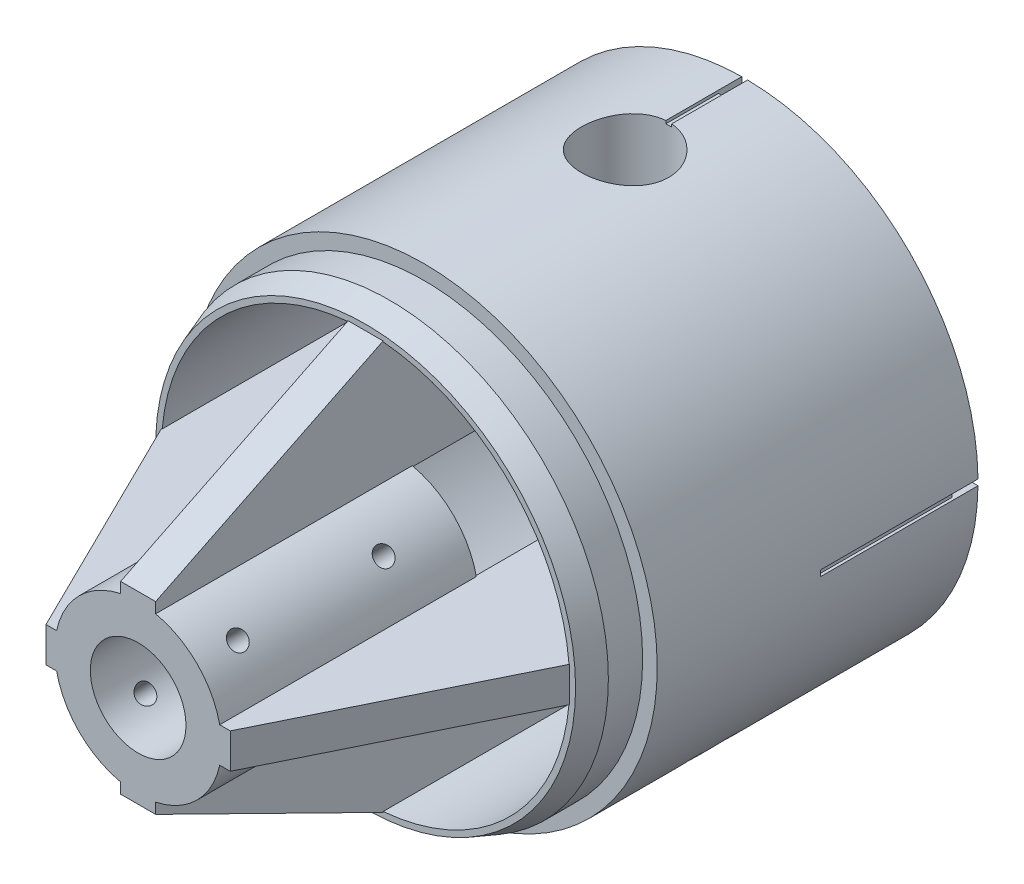
SolidWorks part; units mm, degrees
ref_plane "Piano frontale" through (0, 0, 0) normal (0, 0, 1) x (1, 0, 0)
ref_plane "Piano superiore" through (0, 0, 0) normal (0, 1, 0) x (1, 0, 0)
ref_plane "Piano destro" through (0, 0, 0) normal (1, 0, 0) x (0, 0, -1)
sketch "Schizzo1" plane through (0, 0, 0) normal (0, 0, 1) x (1, 0, 0)
  circle A0 centre (0, 0) radius 40
  circle A1 centre (0, 0) radius 30
  dimension "D1" = 80
  dimension "D2" = 60
extrude "Estrusione-Estrusione1" add sketch "Schizzo1" along normal blind 12.3
sketch "Schizzo2" plane through (0, 0, 12.3) normal (0, 0, 1) x (1, 0, 0)
  circle A0 centre (0, 0) radius 40
  circle A1 centre (0, 0) radius 35
  circle A3 centre (0, 0) radius 40 construction
  dimension "D1" = 5
extrude "Estrusione-Estrusione2" add sketch "Schizzo2" along normal blind 42.7
sketch "Schizzo3" plane through (0, 0, 55) normal (0, 0, 1) x (1, 0, 0)
  circle A0 centre (0, 0) radius 35
  circle A1 centre (0, 0) radius 37.5
  circle A2 centre (0, 0) radius 35 construction
  dimension "D1" = 2.5
extrude "Estrusione-Estrusione3" add sketch "Schizzo3" along normal blind 10
ref_plane "Piano1" through (0, 0, 104) normal (0, 0, 1) x (1, 0, 0)
sketch "Schizzo5" plane through (0, 0, 104) normal (0, 0, 1) x (1, 0, 0)
  circle A0 centre (0, 0) radius 14.3
  circle A1 centre (0, 0) radius 8.2
  dimension "D1" = 28.6
  dimension "D2" = 16.4
extrude "Estrusione-Estrusione4" add sketch "Schizzo5" against normal blind 44 separate body
sketch "Schizzo6" plane through (0, 0, 0) normal (0, 1, 0) x (1, 0, 0)
  line L0 (-35, -26) -> (-35, -65)
  line L1 (-37.5, -65) -> (37.5, -65) construction
  line L2 (-35, -65) -> (-15.8, -104)
  line L3 (-44, -104) -> (44, -104) construction
  line L4 (-15.8, -104) -> (-13.8, -104)
  line L5 (-13.8, -104) -> (-13.8, -26)
  line L6 (-13.8, -26) -> (-35, -26)
  line L7 (-14.3, -60) -> (-14.3, -104) construction
  line L8 (-40, 0) -> (-40, -55) construction
  dimension "D1" = 78
  dimension "D2" = 2
  dimension "D3" = 0.5
  dimension "D4" = 5
extrude "Estrusione-Estrusione5" add sketch "Schizzo6" along normal blind 3 and the other way blind 3
ref_axis "Assi1" through (0, 0, -5.2) along (0, 0, 1)
pattern_circular "RipetizioneCircolare1" count 4 over 360 about axis through (0, 0, -5.2) along (0, 0, 1) of "Estrusione-Estrusione5"
ref_plane "Piano2" through (0, 21.8, 0) normal (0, -1, 0) x (-1, 0, 0)
sketch "Schizzo9" plane through (0, 21.8, 0) normal (0, -1, 0) x (-1, 0, 0)
  line L0 (30, 0) -> (-30, 0) construction
  line L1 (-10, -31) -> (10, -31)
  line L2 (-10, -31) -> (-10, -11)
  line L3 (-10, -11) -> (10, -11)
  line L4 (10, -31) -> (10, -11)
  dimension "D1" = 10
  dimension "D2" = 20
  dimension "D3" = 20
  dimension "D4" = 11
extrude "Estrusione-Estrusione6" add sketch "Schizzo9" against normal blind 15
sketch "Schizzo7" plane through (0, 13.8, 0) normal (0, -1, 0) x (1, 0, 0)
  line L0 (-40, 0) -> (40, 0) construction
  circle A0 centre (0, 20.5) radius 7.5
  dimension "D1" = 15
  dimension "D2" = 20.5
extrude "Taglio-Estrusione1" cut sketch "Schizzo7" against normal through all
ref_plane "Piano3" through (0, 0, 0) normal (0.7071, -0.7071, 0) x (0, 0, 1)
ref_plane "Piano4" through (21.2132, -21.2132, 0) normal (0.7071, -0.7071, 0) x (0, 0, 1)
sketch "Schizzo11" plane through (21.2132, -21.2132, 0) normal (0.7071, -0.7071, 0) x (0, 0, 1)
  circle A0 centre (32, 0) radius 2
  circle A1 centre (38, 0) radius 2
  dimension "D1" = 4
  dimension "D2" = 4
  dimension "D4" = 32
  dimension "D3" = 6
extrude "Taglio-Estrusione2" cut sketch "Schizzo11" along normal through all
sketch "Schizzo12" plane through (0, 0, 60) normal (0, 0, -1) x (-1, 0, 0)
  circle A0 centre (0, 0) radius 8.2
  circle A1 centre (0, 0) radius 4.5
  circle A2 centre (0, 0) radius 8.2 construction
  dimension "D1" = 9
extrude "Estrusione-Estrusione7" add sketch "Schizzo12" against normal blind 4
sketch "Schizzo13" plane through (0, 0, 0) normal (0, 1, 0) x (1, 0, 0)
  line L0 (-2.6, -5.1) -> (-2.6, 0)
  line L1 (-2.6, 0) -> (2.6, 0)
  line L2 (2.6, 0) -> (2.6, -5.1)
  line L3 (40, 0) -> (-40, 0) construction
  circle A0 centre (0, -5.1) radius 2.6
  dimension "D1" = 5.2
  dimension "D2" = 5.1
extrude "Taglio-Estrusione3" cut sketch "Schizzo13" against normal blind 38 contours A0 L2 L1 L0 | A0 region at (0, 0, 1.584) region at (0, 0, 5.1)
sketch "Schizzo14" plane through (0, 0, 0) normal (0, 1, 0) x (1, 0, 0)
  line L0 (30, 0) -> (-30, 0) construction
  line L1 (0.5, 0) -> (-0.5, 0)
  line L2 (0.5, 0) -> (0.5, -4)
  line L3 (0.5, -4) -> (-0.5, -4)
  line L4 (-0.5, 0) -> (-0.5, -4)
  dimension "D1" = 4
  dimension "D2" = 1
  dimension "D3" = 0.5
extrude "Taglio-Estrusione4" cut sketch "Schizzo14" against normal through all
pattern_circular "RipetizioneCircolare2" count 4 over 360 about axis through (0, 0, -5.2) along (0, 0, 1) of "Taglio-Estrusione4", "Taglio-Estrusione3"
ref_plane "Piano6" through (0, -40, 0) normal (0, 1, 0) x (1, 0, 0)
sketch "Schizzo17" plane through (0, -40, 0) normal (0, 1, 0) x (0, 0, -1)
  line L0 (0, -39.9969) -> (0, -0.5) construction
  line L1 (-27, 0.5) -> (0, 0.5)
  line L2 (-27, 0.5) -> (-27, -0.5)
  line L3 (-27, -0.5) -> (0, -0.5)
  line L4 (0, 0.5) -> (0, -0.5)
  dimension "D1" = 27
  dimension "D2" = 1
  dimension "D3" = 0.5
extrude "Taglio-Estrusione5" cut sketch "Schizzo17" along normal blind 0.5
pattern_circular "RipetizioneCircolare3" count 4 over 360 about axis through (0, 0, -5.2) along (0, 0, 1) of "Taglio-Estrusione5"
sketch "Schizzo18" plane through (0, -40, 0) normal (0, 1, 0) x (1, 0, 0)
  line L0 (0.5, 0) -> (0.5, -13.0167) construction
  line L1 (-0.5, 0) -> (0.5, 0)
  line L2 (-0.5, 0) -> (-0.5, -55)
  line L3 (-0.5, -55) -> (0.5, -55)
  line L4 (0.5, 0) -> (0.5, -55)
  line L5 (-37.5, -55) -> (37.5, -55) construction
extrude "Taglio-Estrusione6" cut sketch "Schizzo18" along normal blind 0.5
sketch "Schizzo19" plane through (0, 0, 26) normal (0, 0, -1) x (-1, 0, 0)
  circle A0 centre (-21, 0) radius 1.25
  circle A1 centre (21, 0) radius 1.25
  dimension "D1" = 42
  dimension "D2" = 21
  dimension "D3" = 2.5
  dimension "D4" = 2.5
extrude "Taglio-Estrusione7" cut sketch "Schizzo19" against normal blind 15
ref_plane "Piano7" through (0, 0, 0) normal (0.7071, 0.7071, 0) x (0, 0, 1)
sketch "Schizzo20" plane through (0, 0, 0) normal (0.7071, 0.7071, 0) x (0, 0, 1)
  line L0 (60, 0) -> (104, 0) construction
  line L1 (104, -7.7653) -> (104, 7.7653) construction
  circle A0 centre (97, 0) radius 1.6
  circle A1 centre (72, 0) radius 1.6
  dimension "D1" = 25
  dimension "D2" = 7
  dimension "D3" = 3.2
extrude "Taglio-Estrusione8" cut sketch "Schizzo20" against normal through all both and the other way through all
chamfer "Smusso1" distance 1.5 angle 70 1 edges at (37.5, 0, 65) first distance on face at (37.5, 0, 65)
